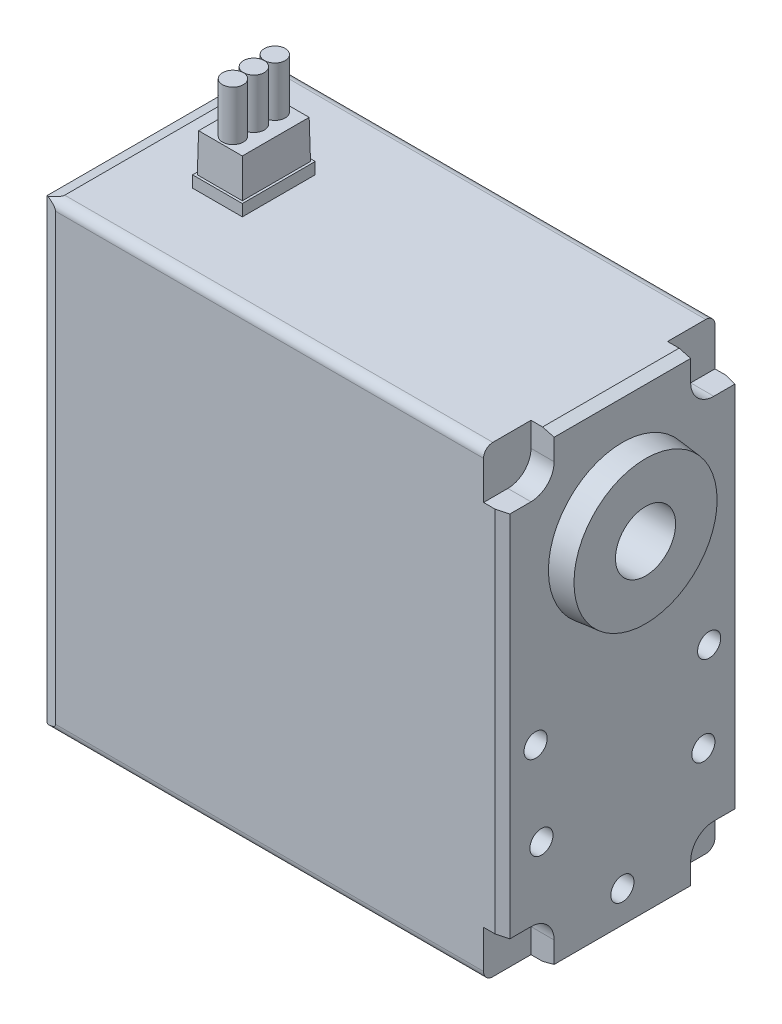
SolidWorks part; units mm, degrees
material "聚脂树脂"
ref_plane "前视基准面" through (0, 0, 0) normal (0, 0, 1) x (1, 0, 0)
ref_plane "上视基准面" through (0, 0, 0) normal (0, 1, 0) x (1, 0, 0)
ref_plane "右视基准面" through (0, 0, 0) normal (1, 0, 0) x (0, 0, -1)
sketch "草图1" plane through (0, 0, 0) normal (0, 1, 0) x (1, 0, 0)
  line L1 (-20, 10) -> (20, 10)
  line L2 (-20, 10) -> (-20, -10)
  line L3 (-20, -10) -> (20, -10)
  line L4 (20, 10) -> (20, -10)
  line L5 (-20, 10) -> (20, -10) construction
  line L6 (-20, -10) -> (20, 10) construction
  point P0 (0, 0)
  dimension "D1" = 20
  dimension "D2" = 40
extrude "凸台-拉伸1" add sketch "草图1" along normal mid plane 40
sketch "草图4" plane through (-20, 0, 0) normal (-1, 0, 0) x (0, 0, 1)
  line L1 (-10, 20) -> (10, 20) construction
  circle A0 centre (0, 10) radius 6.5
  dimension "D1" = 13
  dimension "D2" = 10
extrude "凸台-拉伸2" add sketch "草图4" along normal blind 2
chamfer "倒角1" distance 3 angle 6 1 edges at (-22, 10, 6.5) first distance on face at (-22, 10, 6.5)
sketch "草图5" plane through (20, 0, 0) normal (1, 0, 0) x (0, 0, -1)
  line L0 (-10, 20) -> (10, 20) construction
  circle A0 centre (0, 10) radius 6.5
  dimension "D1" = 13
  dimension "D2" = 10
extrude "凸台-拉伸3" add sketch "草图5" along normal blind 2
chamfer "倒角3" distance 3 angle 6 1 edges at (22, 10, -6.5) first distance on face at (22, 10, -6.5)
sketch "草图7" plane through (22, 0, 0) normal (1, 0, 0) x (0, 0, -1)
  circle A0 centre (0, 10) radius 2.6
  dimension "D1" = 5.2
extrude "切除-拉伸1" cut sketch "草图7" against normal blind 10
sketch "草图8" plane through (-22, 0, 0) normal (-1, 0, 0) x (0, 0, 1)
  circle A0 centre (0, 10) radius 3.75
  circle A1 centre (0, 10) radius 3.45
  circle A2 centre (0, 10) radius 3
  dimension "D1" = 7.5
  dimension "D2" = 6.9
  dimension "D3" = 6
extrude "凸台-拉伸4" add sketch "草图8" along normal blind 4 contours A2 region at (-22, 10, 0)
extrude "凸台-拉伸5" add sketch "草图8<5>" along normal blind 0.2 contours A1 A2 region at (-22, 10, -3.3524)
sketch "草图8<5>" plane through (-22, 0, 0) normal (-1, 0, 0) x (0, 0, 1) same geometry as "草图8"
extrude "凸台-拉伸6" add sketch "草图8<6>" along normal blind 0.1 contours A0 A1 region at (-22, 10, -3.6439)
sketch "草图8<6>" plane through (-22, 0, 0) normal (-1, 0, 0) x (0, 0, 1) same geometry as "草图8"
sketch "草图9" plane through (-26, 0, 0) normal (-1, 0, 0) x (0, 0, 1)
  circle A0 centre (0, 10) radius 1.5
  dimension "D1" = 3
extrude "切除-拉伸2" cut sketch "草图9" against normal blind 5
chamfer "倒角4" distance 1 angle 15 4 edges at (20, -20, 0) (20, 0, -10) (20, 20, 0) (20, 0, 10) first distance on face at (0, -20, 0) first distance on face at (0, 0, -10) first distance on face at (0, 20, 0) first distance on face at (0, 0, 10)
chamfer "倒角5" distance 1 angle 15 4 edges at (-20, -20, 0) (-20, 0, 10) (-20, 20, 0) (-20, 0, -10) first distance on face at (-0.5, -20, 0) first distance on face at (-0.5, 0, 10) first distance on face at (-0.5, 20, 0) first distance on face at (-0.5, 0, -10)
fillet "圆角2" radius 0.8 4 edges at (0, -20, 10) (0, 20, 10) (0, -20, -10) (0, 20, -10)
sketch "草图10" plane through (0, 20, 0) normal (0, 1, 0) x (1, 0, 0)
  line L0 (-20, -9.7321) -> (-20, 9.7321) construction
  line L1 (-14, 3.15) -> (-9.7, 3.15)
  line L2 (-14, 3.15) -> (-14, -3.15)
  line L3 (-14, -3.15) -> (-9.7, -3.15)
  line L4 (-9.7, 3.15) -> (-9.7, -3.15)
  line L5 (-14, 3.15) -> (-9.7, -3.15) construction
  line L6 (-14, -3.15) -> (-9.7, 3.15) construction
  line L7 (-13.8, -2.95) -> (-9.9, -2.95)
  line L8 (-9.9, 2.95) -> (-9.9, -2.95)
  line L9 (-13.8, 2.95) -> (-9.9, 2.95)
  line L10 (-13.8, 2.95) -> (-13.8, -2.95)
  point P0 (-11.85, 0)
  dimension "D1" = 6
  dimension "D2" = 6.3
  dimension "D3" = 4.3
  dimension "D4" = 0.2
extrude "凸台-拉伸7" add sketch "草图10" along normal blind 1 contours L2 L1 L4 L3
extrude "凸台-拉伸8" add sketch "草图10<3>" along normal blind 4.3 contours L9 L10 L7 L8 region at (-11.85, 20, 0)
sketch "草图10<3>" plane through (0, 20, 0) normal (0, 1, 0) x (1, 0, 0) same geometry as "草图10"
chamfer "倒角6" distance 3.5 angle 1 4 edges at (-9.9, 24.3, 0) (-11.85, 24.3, -2.95) (-13.8, 24.3, 0) (-11.85, 24.3, 2.95) first distance on face at (-9.9, 22.65, 0) first distance on face at (-11.85, 22.65, -2.95) first distance on face at (-13.8, 22.65, 0) first distance on face at (-11.85, 22.65, 2.95)
sketch "草图11" plane through (0, 24.3, 0) normal (0, 1, 0) x (1, 0, 0)
  line L0 (-13.7965, -2.9465) -> (-13.7965, 2.9465) construction
  line L1 (-9.9611, 2.8889) -> (-13.7389, 2.8889) construction
  circle A0 centre (-11.85, 0) radius 0.9
  circle A1 centre (-11.85, 1.81) radius 0.9
  circle A2 centre (-11.85, -1.81) radius 0.9
  point P7 (-13.7965, 0)
  point P12 (-11.85, 2.8889)
  dimension "D1" = 1.8
  dimension "D2" = 1.8
  dimension "D4" = 1.8
  dimension "D3" = 1.81
  dimension "D5" = 1.81
extrude "凸台-拉伸10" add sketch "草图11" along normal blind 4.3
sketch "草图12" plane through (20, 0, 0) normal (1, 0, 0) x (0, 0, -1)
  line L0 (9.2, -20) -> (-9.2, -20) construction
  line L1 (-10, -19.2) -> (-10, 19.2) construction
  line L3 (0, 20) -> (0, -20) construction
  circle A0 centre (-7.5, -2.5) radius 1
  circle A5 centre (7.5, -2.5) radius 1
  point P14 (0, 0)
  dimension "D1" = 2
  dimension "D2" = 17.5
  dimension "D3" = 2.5
extrude "切除-拉伸3" cut sketch "草图12" against normal blind 4
sketch "草图13" plane through (-20, 0, 0) normal (-1, 0, 0) x (0, 0, 1)
  line L0 (9.2, -20) -> (-9.2, -20) construction
  line L3 (-10, -19.2) -> (-10, 19.2) construction
  line L4 (0, 20) -> (0, -20) construction
  circle A0 centre (-7.5, -17.5) radius 1
  circle A1 centre (7.5, -17.5) radius 1
  circle A2 centre (-7.5, -2.5) radius 1
  circle A3 centre (-7.5, 17.5) radius 1
  circle A4 centre (7.5, 17.5) radius 1
  circle A5 centre (7.5, -2.5) radius 1
  point P10 (0, 0)
  dimension "D3" = 2
  dimension "D1" = 2.5
  dimension "D2" = 2.5
  dimension "D4" = 2
  dimension "D5" = 2
extrude "切除-拉伸4" cut sketch "草图13" against normal blind 4
sketch "草图14" plane through (20, 0, 0) normal (1, 0, 0) x (0, 0, -1)
  line L0 (-10, -19.2) -> (-10, 19.2) construction
  line L4 (-9.2, 20) -> (9.2, 20) construction
  line L5 (-7.9, 15.9) -> (-10, 15.9)
  line L6 (-5.9, 17.9) -> (-5.9, 20)
  line L7 (-5.9, 20) -> (-10, 20)
  line L8 (-10, 20) -> (-10, 15.9)
  line L9 (10, 0) -> (-10, 0) construction
  line L10 (0, 20) -> (0, -20) construction
  line L11 (9.2, -20) -> (-9.2, -20) construction
  line L12 (7.9, 15.9) -> (10, 15.9)
  line L13 (10, 20) -> (10, 15.9)
  line L14 (5.9, 20) -> (10, 20)
  line L15 (5.9, 17.9) -> (5.9, 20)
  line L16 (5.9, -17.9) -> (5.9, -20)
  line L17 (5.9, -20) -> (10, -20)
  line L18 (10, -20) -> (10, -15.9)
  line L19 (7.9, -15.9) -> (10, -15.9)
  line L20 (-10, -20) -> (-10, -15.9)
  line L21 (-5.9, -20) -> (-10, -20)
  line L22 (-5.9, -17.9) -> (-5.9, -20)
  line L23 (-7.9, -15.9) -> (-10, -15.9)
  circle A0 centre (-7.9, 17.9) radius 2
  circle A1 centre (7.9, 17.9) radius 2
  circle A2 centre (7.9, -17.9) radius 2
  circle A3 centre (-7.9, -17.9) radius 2
  point P15 (0, 0)
  point P21 (0, 0)
  line M10 (-9.7321, 19.7321) -> (-9.7321, -19.7321)
  line M13 (9.7321, 19.7321) -> (-9.7321, 19.7321)
  dimension "D3" = 4
  dimension "D1" = 2.1
  dimension "D2" = 2.1
extrude "切除-拉伸5" cut sketch "草图14" against normal blind 2 contours A0 M13 M10 | A0 L6 M13 | A0 M13 | A0 L6 L7 L8 L5 M13 M10 | A0 M10 | A0 L5 M10 | A0 M13 M10 region at (20, 17.8718, 7.8718) region at (20, 16.2285, 9.3057) region at (20, 15.958, 9.866) region at (20, 19.3057, 6.2285) region at (20, 17.9, 9.7995) region at (20, 19.7995, 7.9) region at (20, 19.4338, 9.4338)
mirror "镜向2" about plane through (0, 0, 0) normal (0, 1, 0) of "切除-拉伸5"
mirror "镜向3" about plane through (0, 0, 0) normal (0, 0, 1) of "镜向2", "切除-拉伸5"
sketch "草图15" plane through (20, 0, 0) normal (1, 0, 0) x (0, 0, -1)
  line L1 (5.9, -20) -> (-5.9, -20) construction
  circle A0 centre (0, -17) radius 1
  circle A1 centre (0, -10) radius 7 construction
  circle A2 centre (-7, -10) radius 1
  circle A3 centre (0, -3) radius 1
  circle A4 centre (7, -10) radius 1
  point P16 (0, -10)
  dimension "D1" = 2
  dimension "D3" = 14
  dimension "D2" = 3
  dimension "D4" = 4
extrude "切除-拉伸7" cut sketch "草图15" against normal blind 4 contours A4 | A0 | A2
ref_plane "基准面1" through (0, 10, 0) normal (0, 1, 0) x (1, 0, 0)
